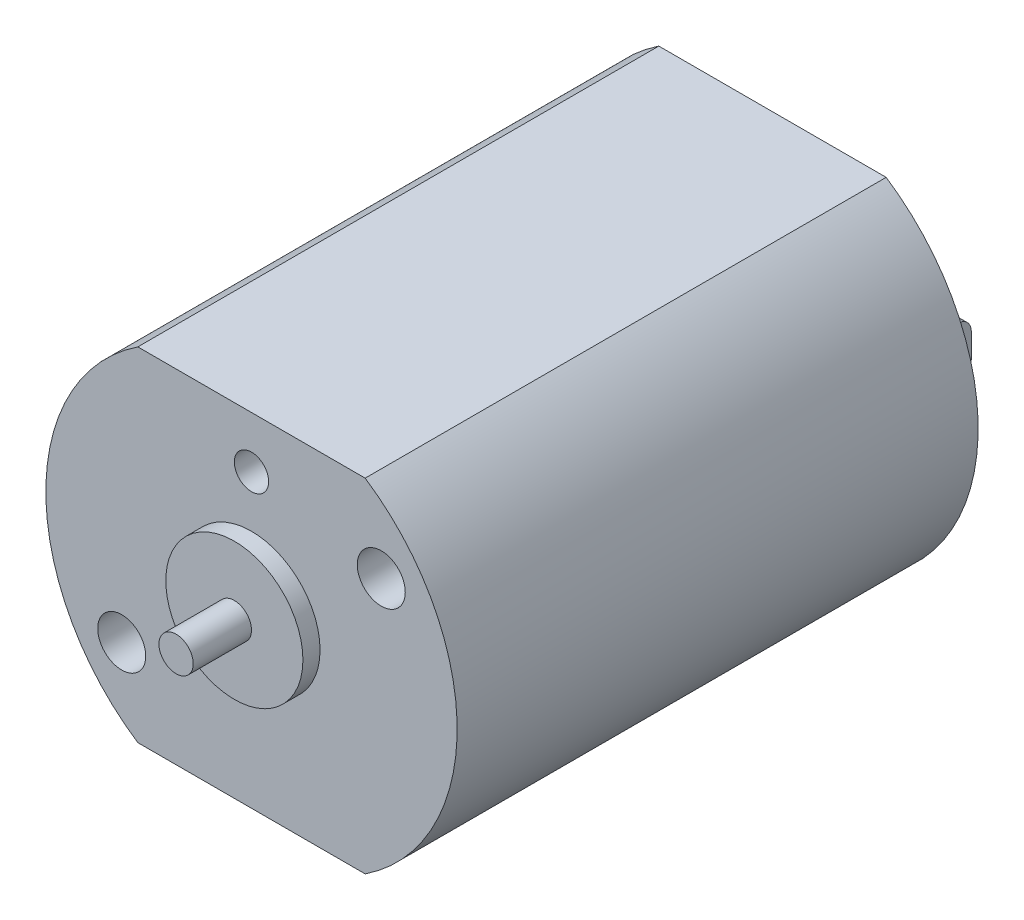
SolidWorks part; units mm, degrees
ref_plane "前视基准面" through (0, 0, 0) normal (0, 0, 1) x (1, 0, 0)
ref_plane "上视基准面" through (0, 0, 0) normal (0, 1, 0) x (1, 0, 0)
ref_plane "右视基准面" through (0, 0, 0) normal (1, 0, 0) x (0, 0, -1)
other "Configuration Table"
sketch "草图1" plane through (0, 0, 0) normal (0, 0, 1) x (1, 0, 0)
  line L0 (3.5, -0.75) -> (3.8, -0.75)
  line L1 (-6, -5) -> (6, -5)
  line L2 (-6, -5) -> (-6, 5)
  line L3 (-6, 5) -> (6, 5)
  line L4 (6, -5) -> (6, 5)
  line L5 (-6, -5) -> (6, 5) construction
  line L6 (-6, 5) -> (6, -5) construction
  line L7 (-3.8, -0.75) -> (-3.5, -0.75)
  line L8 (-3.8, -0.75) -> (-3.8, 0.75)
  line L9 (-3.8, 0.75) -> (-3.5, 0.75)
  line L10 (-3.5, -0.75) -> (-3.5, 0.75)
  line L11 (-3.8, -0.75) -> (-3.5, 0.75) construction
  line L12 (-3.8, 0.75) -> (-3.5, -0.75) construction
  line L13 (3.5, -0.75) -> (3.5, 0.75)
  line L14 (3.5, 0.75) -> (3.8, 0.75)
  line L15 (3.8, -0.75) -> (3.8, 0.75)
  line L16 (-3.5, 0) -> (3.5, 0) construction
  circle A0 centre (0, 0) radius 6
  circle A1 centre (0, 0) radius 2.5
  circle A2 centre (0, 0) radius 1.5
  point P0 (0, 0)
  point P8 (-3.65, 0)
  dimension "D6" = 5
  dimension "D7" = 3
  dimension "D1" = 12
  dimension "D2" = 10
  dimension "D3" = 0.3
  dimension "D4" = 1.5
  dimension "D5" = 7
extrude "凸台-拉伸1" add sketch "草图1" along normal blind 15.2 contours L3 A0 L1 A1 L15 L0 L13 L14 L10 L7 L8 L9 | A1 A2 | A2 | L0 L15 L14 L13 | L7 L10 L9 L8 region at (3.65, 0, 0) region at (-5.1491, -2.7634, 0) region at (-3.65, 0, 0) region at (-2.4293, 0, 0) region at (0, 0, 0)
extrude "凸台-拉伸2" add sketch "草图1<4>" against normal blind 2 contours L13 L14 L15 L0 | L8 L9 L10 L7
sketch "草图1<4>" plane through (0, 0, 0) normal (0, 0, 1) x (1, 0, 0) same geometry as "草图1"
sketch "草图2" plane through (3.8, 0, 0) normal (1, 0, 0) x (0, 0, -1)
  line L0 (0.95, 0) -> (1.05, 0) construction
  line L1 (0.95, 0.45) -> (1.05, 0.45)
  line L2 (0.95, -0.45) -> (1.05, -0.45)
  line L4 (1, 0.75) -> (1, -0.75) construction
  line L5 (2, 0.75) -> (0, 0.75) construction
  line L6 (2, -0.75) -> (0, -0.75) construction
  arc A0 (0.95, 0.45) -> (0.95, -0.45) centre (0.95, 0) ccw
  arc A1 (1.05, -0.45) -> (1.05, 0.45) centre (1.05, 0) ccw
  point P3 (1, 0)
  dimension "D2" = 0.45
  dimension "D1" = 0.1
extrude "切除-拉伸2" cut sketch "草图2" against normal through all
fillet "圆角1" radius 0.4 4 edges at (-3.65, 0.75, -2) (-3.65, -0.75, -2) (3.65, 0.75, -2) (3.65, -0.75, -2)
extrude "凸台-拉伸3" add sketch "草图1<5>" against normal blind 1.2 contours A1 A2 | A2 region at (-2.4293, 0, 0) region at (0, 0, 0)
sketch "草图1<5>" plane through (0, 0, 0) normal (0, 0, 1) x (1, 0, 0) same geometry as "草图1"
extrude "切除-拉伸1" cut sketch "草图1<7>" along normal blind 0.6 from surface contours A2 region at (0, 0, 0) starting at face at (2.5, 0, -1.2)
sketch "草图1<7>" plane through (0, 0, 0) normal (0, 0, 1) x (1, 0, 0) same geometry as "草图1"
fillet "圆角2" radius 0.4 1 edges at (2.5, 0, -1.2)
sketch "草图3" plane through (0, 0, 15.2) normal (0, 0, 1) x (1, 0, 0)
  circle A0 centre (0, 0) radius 2
  circle A1 centre (0, 0) radius 0.5
  dimension "D1" = 4
  dimension "D2" = 1
extrude "凸台-拉伸4" add sketch "草图3" along normal blind 0.5 contours A0
extrude "凸台-拉伸5" add sketch "草图3<3>" along normal blind 2.2 contours A1 region at (0, 0, 15.2)
sketch "草图3<3>" plane through (0, 0, 15.2) normal (0, 0, 1) x (1, 0, 0) same geometry as "草图3"
sketch "草图4" plane through (0, 0, 15.2) normal (0, 0, 1) x (1, 0, 0)
  line L0 (-3.7858, -2.7) -> (3.7858, 2.7) construction
  line L1 (0, 0) -> (0, 5) construction
  line L2 (-3.3166, 5) -> (3.3166, 5) construction
  circle A0 centre (-3.7858, -2.7) radius 0.7
  circle A1 centre (3.7858, 2.7) radius 0.7
  circle A2 centre (0, 3.5) radius 0.5
  point P6 (3.829, 2.6384)
  point P7 (0, 0)
  point P13 (3.3545, 3.2203)
  dimension "D1" = 1.4
  dimension "D2" = 9.3
  dimension "D3" = 1
  dimension "D4" = 3.5
  dimension "D5" = 5.4
extrude "切除-拉伸3" cut sketch "草图4" against normal blind 1
